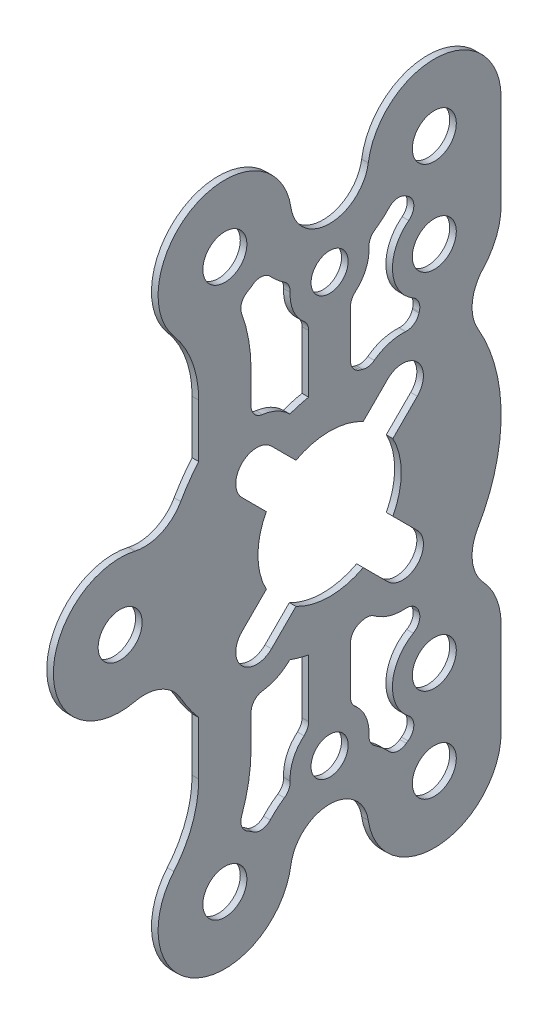
SolidWorks part; units mm, degrees
material "Commercially Pure titanium (Ti-55)  UNS R50550*"
ref_plane "Front Plane" through (0, 0, 0) normal (0, 0, 1) x (1, 0, 0)
ref_plane "Top Plane" through (0, 0, 0) normal (0, 1, 0) x (1, 0, 0)
ref_plane "Right Plane" through (0, 0, 0) normal (1, 0, 0) x (0, 0, -1)
ref_plane "Motor Front Plane" through (39.075, 0, 0) normal (1, 0, 0) x (0, 0, -1)
sketch "Sketch1" plane through (39.075, 0, 0) normal (1, 0, 0) x (0, 0, -1)
  line L0 (-10.6349, 7.0428) -> (-7.6725, 4.0804)
  line L1 (12.7, 21.997) -> (-25.4, 0) construction
  line L3 (12.7, 21.997) -> (12.7, -21.997) construction
  line L4 (-25.4, 0) -> (12.7, -21.997) construction
  line L5 (20.8, 21.997) -> (20.8, 32.6221) construction
  line L6 (-7.0428, 10.6349) -> (-4.0804, 7.6725)
  line L7 (7.6725, -4.0804) -> (10.6349, -7.0428)
  line L8 (4.0804, -7.6725) -> (7.0428, -10.6349)
  line L9 (-10.6349, -7.0428) -> (-7.6725, -4.0804)
  line L10 (-7.0428, -10.6349) -> (-4.0804, -7.6725)
  line L11 (4.0804, 7.6725) -> (7.0428, 10.6349)
  line L12 (7.6725, 4.0804) -> (10.6349, 7.0428)
  circle A0 centre (8.8388, -8.8388) radius 1.65 construction
  circle A1 centre (8.8388, 8.8388) radius 1.65 construction
  circle A2 centre (-8.8388, -8.8388) radius 1.65 construction
  circle A3 centre (-8.8388, 8.8388) radius 1.65 construction
  circle A4 centre (8.8388, -8.8388) radius 1.65 construction
  circle A5 centre (8.8388, 8.8388) radius 1.65 construction
  circle A6 centre (-8.8388, -8.8388) radius 1.65 construction
  circle A7 centre (-8.8388, 8.8388) radius 1.65 construction
  circle A8 centre (0, 0) radius 20.8 construction
  arc A9 (-7.6725, 4.0804) -> (-7.6725, -4.0804) centre (0, 0) ccw
  arc A10 (-7.0199, 10.6117) -> (-10.6349, 7.0428) centre (-8.8388, 8.8388) ccw
  arc A11 (10.6349, 7.0428) -> (7.0428, 10.6349) centre (8.8388, 8.8388) ccw
  arc A12 (7.0428, -10.6349) -> (10.6349, -7.0428) centre (8.8388, -8.8388) ccw
  arc A13 (-10.6349, -7.0428) -> (-7.0199, -10.6117) centre (-8.8388, -8.8388) ccw
  circle A14 centre (-8.8388, 8.8388) radius 3.81 construction
  circle A16 centre (12.7, 21.997) radius 2.667
  circle A18 centre (12.7, -21.997) radius 2.667
  circle A19 centre (-25.4, 0) radius 2.667
  arc A20 (-19.925, -5.9695) -> (4.7928, -20.2403) centre (0, 0) ccw
  arc A21 (-19.925, 5.9695) -> (4.7928, 20.2403) centre (0, 0) cw
  arc A23 (15.1322, 14.2708) -> (15.1322, -14.2708) centre (0, 0) cw
  arc A24 (-19.925, -5.9695) -> (-19.925, 5.9695) centre (-25.4, 0) cw
  arc A25 (4.7928, 20.2403) -> (15.1322, 14.2708) centre (12.7, 21.997) cw
  arc A27 (4.7928, -20.2403) -> (15.1322, -14.2708) centre (12.7, -21.997) ccw
  circle A28 centre (0, 0) radius 25.4 construction
  arc A29 (7.6725, -4.0804) -> (7.6725, 4.0804) centre (0, 0) ccw
  arc A30 (4.0804, 7.6725) -> (-4.0804, 7.6725) centre (0, 0) ccw
  arc A31 (-4.0804, -7.6725) -> (4.0804, -7.6725) centre (0, 0) ccw
  dimension "D1" = 41.6
  dimension "D2" = 5.08
  dimension "D3" = 7.62
  dimension "D4" = 5.334
  dimension "D5" = 50.8
extrude "Boss-Extrude1" add sketch "Sketch1" along normal blind 0.8 contours A20 A27 A23 A25 A21 A24 A31 L10 A13 L9 A9 L0 A10 L6 A30 L11 A11 L12 A29 L7 A12 L8 A16 A18 A19 region at (39.075, 0, 32.6893)
fillet "Fillet1" radius 5.08 6 edges at (39.475, 5.9695, 19.925) (39.475, -14.2708, -15.1322) (39.475, -20.2403, -4.7928) (39.475, -5.9695, 19.925) (39.475, 20.2403, -4.7928) (39.475, 14.2708, -15.1322)
sketch "Sketch2" plane through (39.875, 0, 0) normal (1, 0, 0) x (0, 0, -1)
  line L0 (-12.7, -33.3375) -> (-12.7, 33.3375) construction
  line L5 (0, 0) -> (-12.7, 0) construction
  line L6 (0, 0) -> (0, 30.48) construction
  line L11 (12.7, 33.3375) -> (12.7, 21.997) construction
  line L13 (20.8, 33.3375) -> (20.8, 21.997)
  line L14 (-15.875, 19.8978) -> (-15.875, 13.4397)
  arc A16 (18.6368, 16.4866) -> (4.9595, 24.3833) centre (12.7, 21.997) ccw construction
  arc A18 (0.0843, 20.7998) -> (-18.0553, 10.3269) centre (0, 0) ccw construction
  circle A22 centre (12.7, 21.997) radius 2.667 construction
  arc A24 (-4.6874, 34.5243) -> (-18.8821, 28.1038) centre (-12.7, 33.3375) ccw
  circle A27 centre (-12.7, 33.3375) radius 2.667
  circle A32 centre (12.7, 33.3375) radius 2.667
  arc A33 (4.6874, 34.5243) -> (20.8, 33.3375) centre (12.7, 33.3375) cw
  arc A35 (-4.6874, 34.5243) -> (4.6874, 34.5243) centre (0, 35.2185) ccw
  arc A37 (0.0843, 20.7998) -> (4.9595, 24.3833) centre (0.1049, 25.8798) ccw construction
  arc A38 (20.8, 21.997) -> (4.9595, 24.3833) centre (12.7, 21.997) ccw
  arc A39 (0.0843, 20.7998) -> (4.9595, 24.3833) centre (0.1049, 25.8798) ccw
  arc A40 (-18.8821, 28.1038) -> (-15.875, 19.8978) centre (-28.575, 19.8978) cw
  arc A41 (0.0843, 20.7998) -> (-15.875, 13.4397) centre (0, 0) ccw
  dimension "D3" = 30.48
  dimension "D1" = 6.35
  dimension "D4" = 12.7
  dimension "D2" = 66.675
extrude "Boss-Extrude2" add sketch "Sketch2" against normal up to surface (0.8 mm away) contours A38 A39 A41 L14 A40 A24 A35 A33 L13 | A27 | A32 up to face at (39.075, 0, 0)
sketch "Sketch3" plane through (39.075, 0, 0) normal (-1, 0, 0) x (0, 0, 1)
  line L0 (-11.2696, 17.1226) -> (-10.448, 14.3226)
  line L1 (-12.7, 33.3375) -> (-12.7, 21.997)
  line L2 (9.525, 14.5125) -> (9.525, 19.8978)
  line L4 (15.875, 13.4397) -> (15.875, 19.8978) construction
  circle A0 centre (-12.7, 21.997) radius 5.08
  circle A1 centre (-8.8388, 8.8388) radius 5.715
  circle A2 centre (8.8388, 8.8388) radius 5.715
  circle A3 centre (12.7, 33.3375) radius 5.715
  circle A4 centre (-12.7, 33.3375) radius 5.715
  arc A5 (-8.1987, 29.8162) -> (8.1987, 29.8162) centre (0, 35.2185) ccw
  arc A7 (-9.5127, 28.5938) -> (-9.597, 26.0192) centre (-8.6273, 27.2762) ccw
  circle A8 centre (0, 0) radius 13.77
  arc A10 (9.525, 19.8978) -> (11.2461, 27.8105) centre (28.575, 19.8978) cw
  arc A12 (4.0804, 7.6725) -> (-4.0804, 7.6725) centre (0, 0) ccw construction
  arc A13 (18.8821, 28.1038) -> (15.875, 19.8978) centre (28.575, 19.8978) ccw construction
  arc A14 (-4.6874, 34.5243) -> (4.6874, 34.5243) centre (0, 35.2185) ccw construction
  dimension "D1" = 11.43
  dimension "D2" = 10.16
  dimension "D3" = 5.08
  dimension "D4" = 1.5875
  dimension "D5" = 5.08
  dimension "D7" = 11.43
  dimension "D6" = 6.35
extrude "Cut-Extrude1" cut sketch "Sketch3" against normal through all contours L2 A10 A3 A5 A4 A7 A0 L0 A1 A8 A2 region at (39.075, 20.4975, 0.3413)
sketch "Sketch4" plane through (39.075, 0, 0) normal (-1, 0, 0) x (0, 0, 1)
  line L0 (0, 0) -> (0, 25.4) construction
  circle A0 centre (0, 25.4) radius 2.2479 construction
  circle A1 centre (0, 25.4) radius 4.7879
  circle A2 centre (0, 25.4) radius 3.9624 construction
  dimension "D1" = 4.4958
  dimension "D2" = 2.54
  dimension "D3" = 7.9248
  dimension "D4" = 25.4
extrude "Boss-Extrude3" add sketch "Sketch4" against normal up to surface (0.8 mm away) up to face at (39.875, 33.3375, -10.033)
hole_wizard "#8 Clearance Hole1" positions "Sketch7" profile "Sketch6" hole size "#8" standard "ANSI Inch" end condition up to next
sketch "Sketch7" plane through (39.075, 0, 0) normal (-1, 0, 0) x (0, 0, 1)
  point P0 (0, 25.4)
sketch "Sketch6" plane through (39.075, 25.4, 0) normal (0, 1, 0) x (0, 0, 1)
  line L0 (0, 0) -> (0, 0.8)
  line L1 (0, 0.8) -> (2.2479, 0.8)
  line L2 (2.2479, 0.8) -> (2.2479, 0)
  line L5 (2.2479, 0) -> (0, 0)
  line L11 (0, -6.35) -> (0, 107.95) construction
  dimension "Thru Hole Dia." = 4.4958
  dimension "Thru Hole Depth" = 0.8
sketch "Sketch9" plane through (39.075, 0, 0) normal (-1, 0, 0) x (0, 0, 1)
  line L0 (0, 23.1521) -> (0, 8.69)
  circle A2 centre (0, 25.4) radius 2.2479 construction
  arc A3 (4.0804, 7.6725) -> (-4.0804, 7.6725) centre (0, 0) ccw construction
extrude "Extrude-Thin1" add sketch "Sketch9" against normal up to surface (0.8 mm away) thin up to face at (39.875, 25.4, -2.2479) thin type mid plane wall 5.08
fillet "Fillet3" radius 1.5875 12 edges at (39.475, 12.8997, -4.8176) (39.475, 14.3226, -10.448) (39.475, 17.1226, -11.2696) (39.475, 29.8162, 8.1987) (39.475, 27.8105, 11.2461) (39.475, 14.5125, 9.525) (39.475, 29.8162, -8.1987) (39.475, 21.3414, 2.54) (39.475, 21.3414, -2.54) (39.475, 13.5337, -2.54) (39.475, 26.5674, -4.6434) (39.475, 26.5674, 4.6434)
mirror "Mirror1" about plane through (0, 0, 0) normal (0, 1, 0) of "Boss-Extrude2", "Cut-Extrude1", "Boss-Extrude3", "#8 Clearance Hole1", "Extrude-Thin1", "Fillet3"
equation "\"D1@Sketch1\"=41.6mm"
